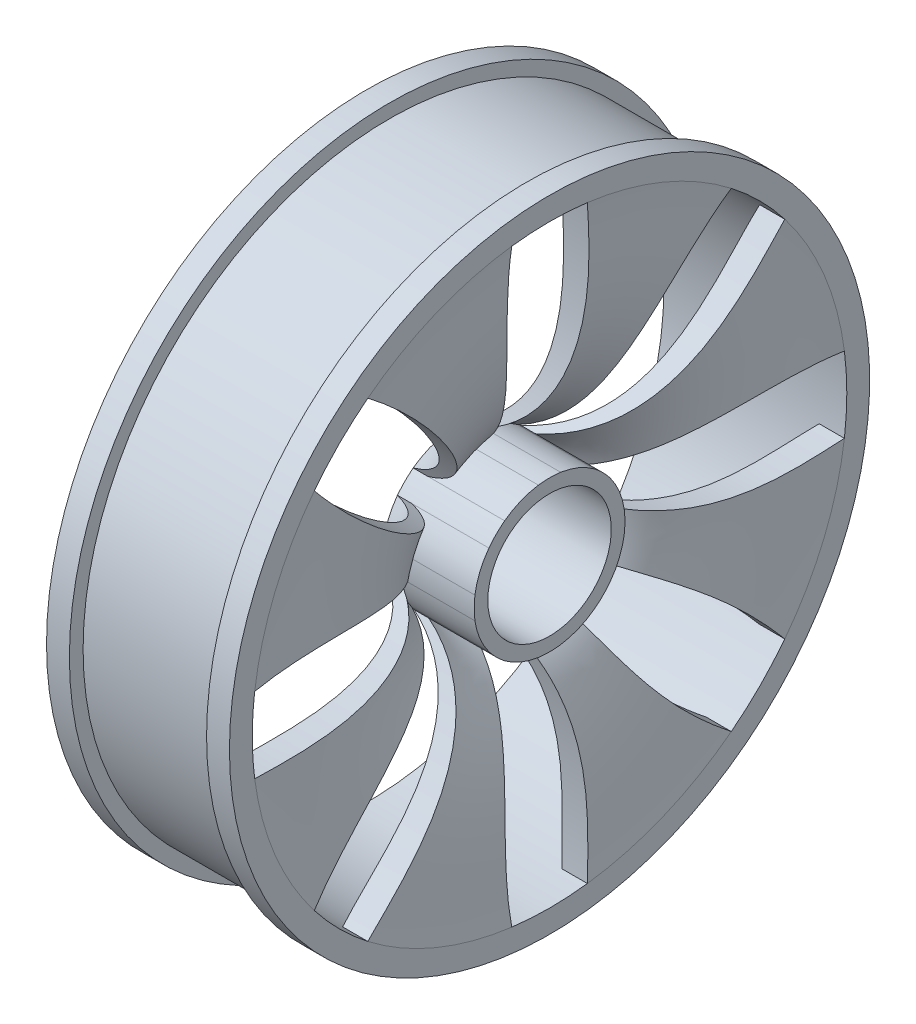
SolidWorks part; units mm, degrees
material "1023 Carbon Steel Sheet (SS)"
ref_plane "Front Plane" through (0, 0, 0) normal (0, 0, 1) x (1, 0, 0)
ref_plane "Top Plane" through (0, 0, 0) normal (0, 1, 0) x (1, 0, 0)
ref_plane "Right Plane" through (0, 0, 0) normal (1, 0, 0) x (0, 0, -1)
sketch "Sketch1" plane through (0, 0, 0) normal (0, 0, 1) x (1, 0, 0)
  line L0 (0, 0) -> (83.9712, 0) construction
  line L1 (-20, 65) -> (13.1537, 65)
  line L2 (20, 65) -> (20, 70)
  line L3 (20, 70) -> (15, 70)
  line L4 (15, 70) -> (15, 67)
  line L5 (15, 67) -> (-15, 67)
  line L7 (0, 0) -> (0, 21.9627) construction
  line L8 (-15, 70) -> (-15, 67)
  line L9 (-20, 70) -> (-15, 70)
  line L10 (-20, 65) -> (-20, 70)
  line L17 (13.1537, 65) -> (14.4947, 65)
  line L18 (0, 13.5) -> (20, 13.5)
  line L19 (20, 13.5) -> (20, 16.5)
  line L20 (20, 16.5) -> (3.1757, 16.5)
  line L21 (0, 16.5) -> (0, 13.5)
  spline S0 degree 3 poles (20, 65) (18.8064, 48.991) (21.6541, 24.8964) (3.1757, 16.5) knots 0 0 0 0 1 1 1 1
  spline S1 degree 3 poles (14.4947, 65) (12.5022, 49.4908) (18.4668, 25.2484) (0, 16.5) knots 0 0 0 0 1 1 1 1
  dimension "D1" = 40
  dimension "D2" = 30
  dimension "D3" = 3
  dimension "D4" = 67
  dimension "D5" = 2
  dimension "D7" = 3
  dimension "D6" = 20
  dimension "D8" = 13.5
revolve "Revolve1" add sketch "Sketch1" angle 360 about L0
ref_plane "Plane1" through (30, 0, 0) normal (1, 0, 0) x (0, 0, -1)
sketch "Sketch2" plane through (30, 0, 0) normal (1, 0, 0) x (0, 0, -1)
  circle A12 centre (0, 0) radius 65 construction
  circle A13 centre (0, 0) radius 16.5 construction
  circle A14 centre (0, 0) radius 16.5 construction
  arc A15 (-8.2695, 64.4718) -> (8.2695, 64.4718) centre (0, 0) cw
  arc A16 (-2.435, 16.3193) -> (2.435, 16.3193) centre (0, -1.5152) cw
  spline S0 degree 2 poles (-8.2695, 64.4718) (-10.5417, 39.8353) (-2.435, 16.3193) knots 0 0 0 1 1 1
  spline S1 degree 2 poles (8.2695, 64.4718) (11.4096, 39.7562) (2.435, 16.3193) knots 0 0 0 1 1 1
extrude "Cut-Extrude2" cut sketch "Sketch2" against normal through all
pattern_circular "CirPattern2" count 8 over 360 about axis through (20, 0, 0) along (-1, 0, 0) of "Cut-Extrude2"
scale "Scale1" scale about centroid uniform scaling yes scale factor 0.5
